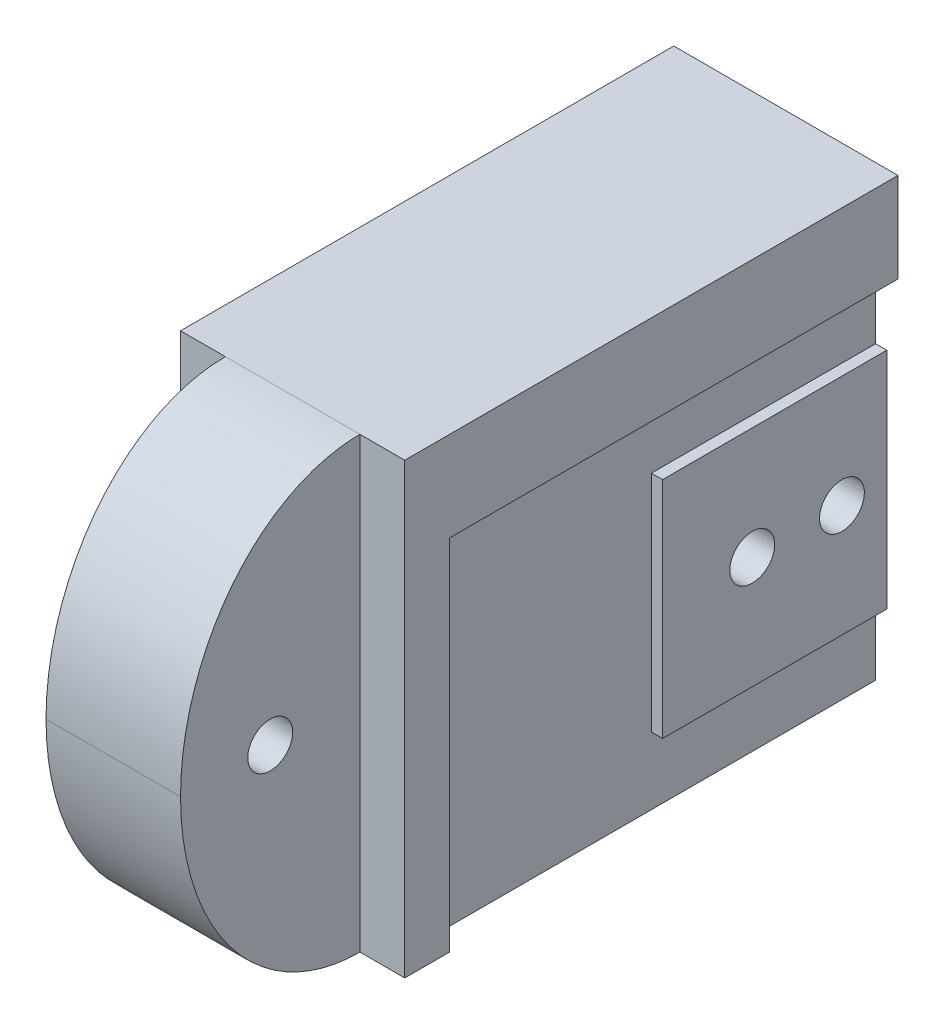
SolidWorks part; units mm, degrees
ref_plane "Ebene vorne" through (0, 0, 0) normal (0, 0, 1) x (1, 0, 0)
ref_plane "Ebene oben" through (0, 0, 0) normal (0, 1, 0) x (1, 0, 0)
ref_plane "Ebene rechts" through (0, 0, 0) normal (1, 0, 0) x (0, 0, -1)
sketch "Skizze1" plane through (0, 0, 0) normal (1, 0, 0) x (0, 0, -1)
  line L1 (-106.9542, 40.537) -> (43.0458, 40.537)
  line L2 (-106.9542, 40.537) -> (-106.9542, -59.463)
  line L3 (-106.9542, -59.463) -> (43.0458, -59.463)
  line L4 (43.0458, 40.537) -> (43.0458, -59.463)
  dimension "D1" = 150
  dimension "D2" = 100
extrude "Aufsatz-Linear austragen1" add sketch "Skizze1" along normal blind 50
sketch "Skizze2" plane through (50, 0, 0) normal (1, 0, 0) x (0, 0, -1)
  line L1 (43.0458, -59.463) -> (-56.9542, -59.463)
  line L2 (43.0458, -59.463) -> (43.0458, 20.537)
  line L3 (43.0458, 20.537) -> (-56.9542, 20.537)
  line L4 (-56.9542, -59.463) -> (-56.9542, 20.537)
  dimension "D1" = 100
  dimension "D2" = 80
extrude "Schnitt-Linear austragen1" cut sketch "Skizze2" against normal blind 5
sketch "Skizze3" plane through (45, 0, 0) normal (1, 0, 0) x (0, 0, -1)
  line L0 (43.0458, -59.463) -> (43.0458, 20.537) construction
  line L1 (-56.9542, -59.463) -> (43.0458, -59.463) construction
  line L2 (43.0458, 5.537) -> (-6.9542, 5.537)
  line L3 (43.0458, 5.537) -> (43.0458, -44.463)
  line L4 (43.0458, -44.463) -> (-6.9542, -44.463)
  line L5 (-6.9542, 5.537) -> (-6.9542, -44.463)
  dimension "D1" = 50
  dimension "D2" = 50
  dimension "D3" = 15
extrude "Aufsatz-Linear austragen2" add sketch "Skizze3" along normal blind 2.5
sketch "Skizze4" plane through (47.5, 0, 0) normal (1, 0, 0) x (0, 0, -1)
  line L0 (43.0458, -44.463) -> (43.0458, 5.537) construction
  circle A0 centre (33.0458, -19.463) radius 5
  circle A1 centre (13.0458, -19.463) radius 5
  dimension "D1" = 10
  dimension "D2" = 20
extrude "Schnitt-Linear austragen2" cut sketch "Skizze4" against normal blind 10
sketch "Skizze5" plane through (0, 0, 106.9542) normal (0, 0, 1) x (1, 0, 0)
  line L0 (50, -59.463) -> (0, -59.463) construction
  line L1 (0, 40.537) -> (10, 40.537)
  line L2 (0, 40.537) -> (0, -59.463)
  line L3 (0, -59.463) -> (10, -59.463)
  line L4 (10, 40.537) -> (10, -59.463)
  line L5 (25, 40.537) -> (25, -59.463) construction
  line L6 (50, 40.537) -> (0, 40.537) construction
  line L7 (50, -59.463) -> (40, -59.463)
  line L8 (40, 40.537) -> (40, -59.463)
  line L9 (50, 40.537) -> (40, 40.537)
  line L10 (50, 40.537) -> (50, -59.463)
  dimension "D1" = 10
extrude "Schnitt-Linear austragen3" cut sketch "Skizze5" against normal blind 40
sketch "Skizze6" plane through (40, 0, 0) normal (1, 0, 0) x (0, 0, -1)
  line L0 (-106.9542, 40.537) -> (-106.9542, -59.463) construction
  circle A0 centre (-86.9542, -9.463) radius 5
  dimension "D1" = 20
extrude "Schnitt-Linear austragen4" cut sketch "Skizze6" against normal blind 40
fillet "Verrundung1" radius 40 2 edges at (25, -59.463, 106.9542) (25, 40.537, 106.9542) second distance 50 first distance on face at (29, -59.463, 50.9542) first distance on face at (25, 40.537, 49.4542)
